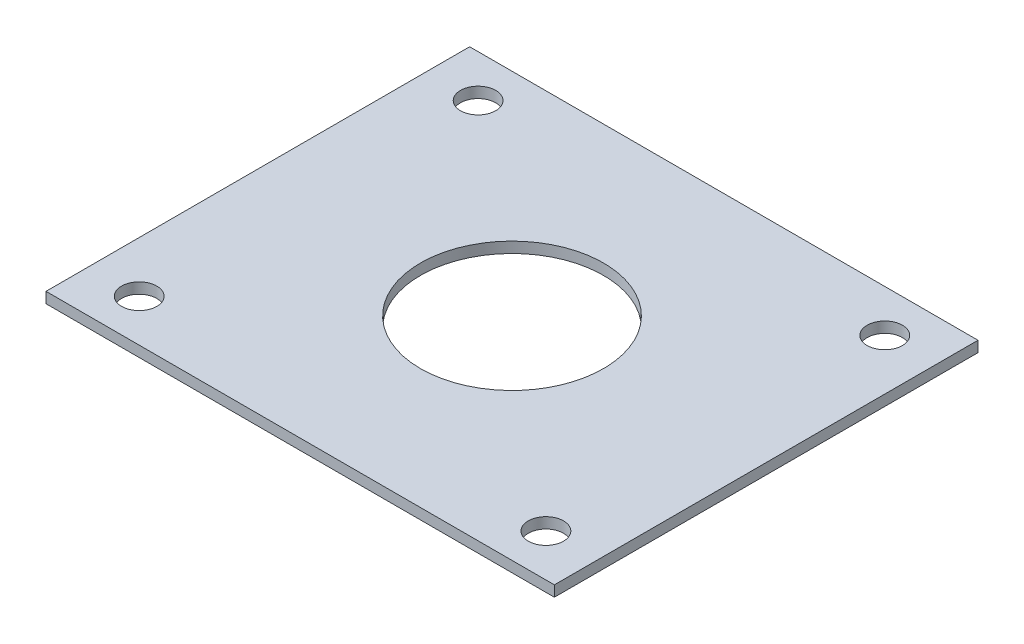
SolidWorks part; units mm, degrees
ref_plane "Front Plane" through (0, 0, 0) normal (0, 0, 1) x (1, 0, 0)
ref_plane "Top Plane" through (0, 0, 0) normal (0, 1, 0) x (1, 0, 0)
ref_plane "Right Plane" through (0, 0, 0) normal (1, 0, 0) x (0, 0, -1)
sketch "Sketch1" plane through (0, 0, 0) normal (0, 1, 0) x (1, 0, 0)
  line L0 (30, 25) -> (0, 25) construction
  line L1 (-37.5, -31.25) -> (37.5, -31.25)
  line L2 (-37.5, -31.25) -> (-37.5, 31.25)
  line L3 (-37.5, 31.25) -> (37.5, 31.25)
  line L4 (37.5, -31.25) -> (37.5, 31.25)
  line L5 (-37.5, -31.25) -> (37.5, 31.25) construction
  line L6 (-37.5, 31.25) -> (37.5, -31.25) construction
  line L7 (0, 25) -> (0, 0) construction
  line L8 (-37.5, 0) -> (37.5, 0) construction
  circle A0 centre (0, 0) radius 13.5
  circle A1 centre (30, 25) radius 2.6
  circle A2 centre (-30, 25) radius 2.6
  circle A3 centre (30, -25) radius 2.6
  circle A4 centre (-30, -25) radius 2.6
  point P0 (0, 0)
  dimension "D3" = 27
  dimension "D6" = 5.2
  dimension "D1" = 62.5
  dimension "D2" = 75
  dimension "D4" = 30
  dimension "D5" = 25
extrude "Boss-Extrude1" add sketch "Sketch1" along normal blind 0.7937 and the other way blind 0.7937
